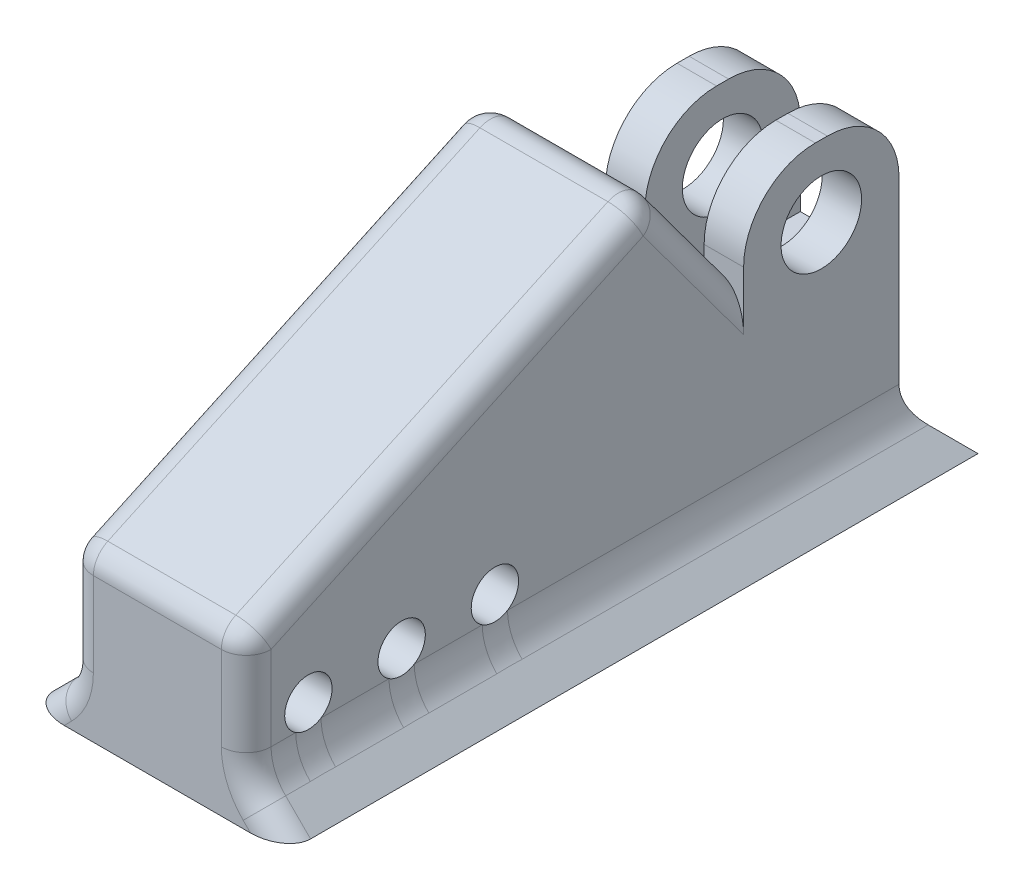
SolidWorks part; units mm, degrees
ref_plane "Front Plane" through (0, 0, 0) normal (0, 0, 1) x (1, 0, 0)
ref_plane "Top Plane" through (0, 0, 0) normal (0, 1, 0) x (1, 0, 0)
ref_plane "Right Plane" through (0, 0, 0) normal (1, 0, 0) x (0, 0, -1)
sketch "Sketch1" plane through (0, 0, 0) normal (0, 0, 1) x (1, 0, 0)
  line L1 (-14.29, -25) -> (14.29, -25)
  line L2 (-14.29, -25) -> (-14.29, 25)
  line L3 (-14.29, 25) -> (14.29, 25)
  line L4 (14.29, -25) -> (14.29, 25)
  line L5 (-14.29, -25) -> (14.29, 25) construction
  line L6 (-14.29, 25) -> (14.29, -25) construction
  point P0 (0, 0)
  dimension "D1" = 50
  dimension "D2" = 28.58
extrude "Boss-Extrude1" add sketch "Sketch1" along normal mid plane 25
sketch "Sketch2" plane through (0, 0, 12.5) normal (0, 0, 1) x (-1, 0, 0)
  line L1 (-7.94, -0.775) -> (1.59, -0.775)
  line L2 (-7.94, -0.775) -> (-7.94, -25)
  line L3 (-7.94, -25) -> (1.59, -25)
  line L4 (1.59, -0.775) -> (1.59, -25)
  line L5 (7.94, -0.775) -> (14.29, -0.775)
  line L6 (7.94, -0.775) -> (7.94, -25)
  line L7 (7.94, -25) -> (14.29, -25)
  line L8 (14.29, -0.775) -> (14.29, -25)
  line L10 (-14.29, -25) -> (14.29, -25) construction
  line L11 (14.29, -25) -> (14.29, 25) construction
  line L12 (-14.29, 25) -> (-14.29, -25) construction
  dimension "D1" = 6.35
  dimension "D2" = 6.35
  dimension "D3" = 24.225
  dimension "D4" = 6.35
extrude "Cut-Extrude1" cut sketch "Sketch2" against normal through all
fillet "Fillet1" radius 11.53 4 edges at (-4.765, 25, -12.5) (-4.765, 25, 12.5) (11.115, 25, 12.5) (11.115, 25, -12.5)
sketch "Sketch3" plane through (14.29, 0, 0) normal (1, 0, 0) x (0, 0, -1)
  line L0 (-11.4063, 13.47) -> (20.1617, 13.47) construction
  line L1 (0, 37.5) -> (0, -49962.5) construction
  line L2 (-0.97, 25) -> (0.97, 25) construction
  circle A0 centre (0, 13.47) radius 6.477
  point P9 (0, 25)
  dimension "D1" = 12.954
extrude "Cut-Extrude2" cut sketch "Sketch3" against normal through all
sketch "Sketch4" plane through (14.29, 0, 0) normal (1, 0, 0) x (0, 0, -1)
  line L0 (-15.659, -25) -> (49984.341, -25) construction
  line L2 (-12.5, -25) -> (12.5, -25) construction
  line L3 (18.85, -25) -> (12.5, -18.65)
  line L4 (12.5, -25) -> (12.5, 13.47) construction
  line L5 (12.5, -18.65) -> (12.5, -25)
  line L6 (12.5, -25) -> (18.85, -25)
  dimension "D1" = 6.35
  dimension "D2" = 45
extrude "Boss-Extrude2" add sketch "Sketch4" against normal up to surface (28.58 mm away) up to face at (-14.29, -12.1125, 0)
sketch "Sketch5" plane through (0, 0, 12.5) normal (0, 0, 1) x (1, 0, 0)
  line L0 (-1.59, 0.775) -> (7.94, 0.775) construction
  line L1 (-14.29, -25) -> (14.29, -25)
  line L2 (-14.29, -25) -> (-14.29, 0.775)
  line L3 (-14.29, 0.775) -> (14.29, 0.775)
  line L4 (14.29, -25) -> (14.29, 0.775)
  line L5 (14.29, -25) -> (14.29, 13.47) construction
extrude "Boss-Extrude3" add sketch "Sketch5" along normal blind 80
sketch "Sketch6" plane through (14.29, 0, 0) normal (1, 0, 0) x (0, 0, -1)
  line L0 (-82.5, 0.775) -> (-82.5, -27.4392) construction
  line L1 (-92.5, -25) -> (-92.5, 0.775) construction
  line L2 (-39.7474, -12.1125) -> (-45.2025, -12.1125) construction
  circle A0 centre (-82.5, -12.1125) radius 3.81
  circle A1 centre (-67.5, -12.1125) radius 3.81
  circle A2 centre (-52.5, -12.1125) radius 3.81
  dimension "D1" = 7.62
  dimension "D2" = 10
  dimension "D3" = 15
  dimension "D4" = 15
extrude "Cut-Extrude3" cut sketch "Sketch6" against normal through all both and the other way through all
sketch "Sketch7" plane through (0, 0, -12.5) normal (0, 0, -1) x (-1, 0, 0)
  line L0 (-14.29, -25) -> (-20.64, -25)
  line L1 (-20.64, -25) -> (-14.29, -18.65)
  line L2 (-14.29, -18.65) -> (-14.29, 13.47) construction
  line L3 (14.29, -25) -> (-14.29, -25) construction
  line L4 (-14.29, -25) -> (-14.29, -18.65) construction
  line L5 (-14.29, -18.65) -> (-14.29, -25)
  dimension "D1" = 45
  dimension "D2" = 6.35
extrude "Boss-Extrude4" add sketch "Sketch7" against normal up to surface and the other way up to surface up to face at (0, -12.1125, 92.5) other way up to face at (0, -21.825, -15.675)
mirror "Mirror2" about plane through (0, 0, 0) normal (1, 0, 0) of "Boss-Extrude4"
hole_wizard "Trous de centrage Ø5.0mm1" positions "Sketch9" profile "Sketch11" hole size "Ø5.0" standard "Ansi Metric"
sketch "Sketch9" plane through (0, -25, 0) normal (0, -1, 0) x (-1, 0, 0)
  point P0 (-7.5, 0.5343)
  point P3 (7.5, 0.5343)
  point P6 (7.5, -14.4657)
  point P9 (-7.5, -14.4657)
  point P12 (-7.5, -29.4657)
  point P14 (7.5, -29.4657)
  point P16 (7.5, -44.4657)
  point P18 (-7.5, -44.4657)
  dimension "D1" = 15
  dimension "D2" = 15
  dimension "D3" = 15
  dimension "D4" = 15
sketch "Sketch11" plane through (7.5, -25, -0.5343) normal (1, 0, 0) x (0, 0, -1)
  line L0 (0, 0) -> (0, 11.5022)
  line L1 (0, 11.5022) -> (2.5, 10)
  line L2 (2.5, 10) -> (2.5, 0)
  line L5 (2.5, 0) -> (0, 0)
  line L10 (0, 11.5022) -> (-2.5, 10) construction
  line L11 (0, -6.35) -> (0, 107.95) construction
  dimension "Hole Dia." = 5
  dimension "Hole Depth" = 10
  dimension "Drill Angle" = 118
sketch "Esquisse1" plane through (14.29, 0, 0) normal (1, 0, 0) x (0, 0, -1)
  line L1 (-27.3706, 30.8714) -> (-12.5, 10.775)
  line L5 (-92.5, 0.775) -> (-27.3706, 30.8714)
  line L7 (-92.5, 0.775) -> (-12.5, 0.775)
  line L8 (-12.5, 0.775) -> (-12.5, 10.775)
  line L9 (-12.5, 0.775) -> (-12.5, 13.47) construction
  point P1 (-12.5, 13.47)
  point P3 (-12.5, 10.1401)
  point P8 (-28.867, 32.8937)
  dimension "D1" = 10
  dimension "D2" = 25
  dimension "D3" = 36.5
extrude "Boss.-Extru.1" add sketch "Esquisse1" against normal up to surface (28.58 mm away) up to face at (-14.29, -12.1125, 48.69)
fillet "Fillet2" radius 8 3 edges at (-14.29, -18.65, 40) (14.29, -18.65, 40) (0, -18.65, -12.5)
fillet "Fillet4" radius 4 13 edges at (-14.29, 0.775, 0) (-18.6366, -22.9966, 92.5) (-14.899, -18.3978, 92.5) (18.6366, -22.9966, 92.5) (14.899, -18.3978, 92.5) (-14.29, -7.2806, 92.5) (14.29, -7.2806, 92.5) (-14.29, 20.8232, 19.9353) (14.29, 20.8232, 19.9353) (0, 0.775, 92.5) (-14.29, 15.8232, 59.9353) (14.29, 15.8232, 59.9353) (0, 30.8714, 27.3706)
